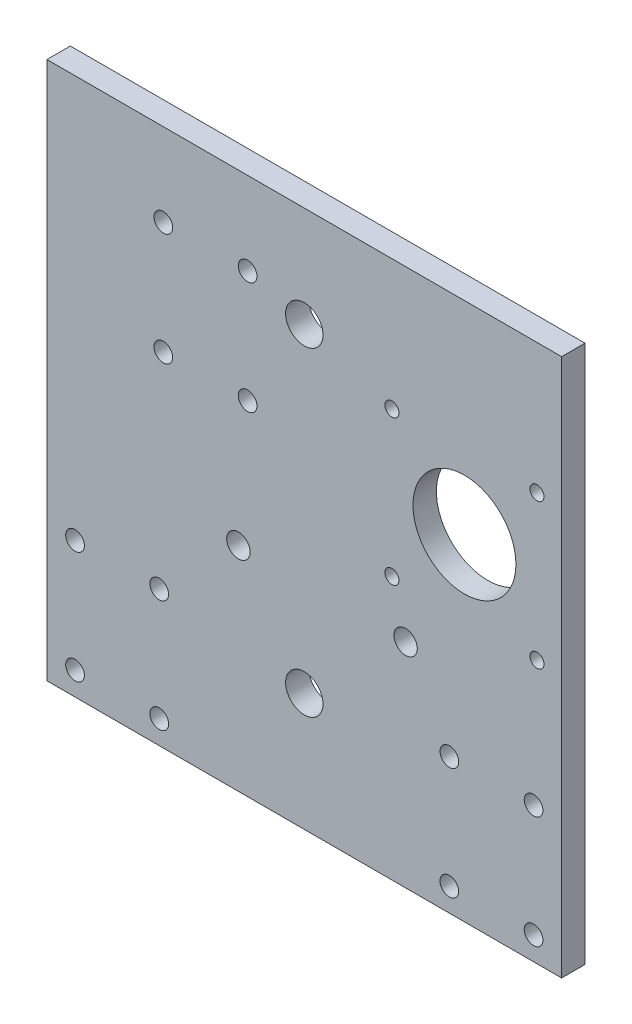
SolidWorks part; units mm, degrees
ref_plane "Front Plane" through (0, 0, 0) normal (0, 0, 1) x (1, 0, 0)
ref_plane "Top Plane" through (0, 0, 0) normal (0, 1, 0) x (1, 0, 0)
ref_plane "Right Plane" through (0, 0, 0) normal (1, 0, 0) x (0, 0, -1)
sketch "Sketch1" plane through (0, 0, 0) normal (0, 0, 1) x (1, 0, 0)
  line L0 (-49, -33.3512) -> (-31, -33.3512) construction
  line L1 (-55, 52.6488) -> (55, 52.6488)
  line L2 (-55, 52.6488) -> (-55, -62.3512)
  line L3 (-55, -62.3512) -> (55, -62.3512)
  line L4 (55, 52.6488) -> (55, -62.3512)
  line L5 (-31, -33.3512) -> (-31, -57.3512) construction
  line L6 (-31, -57.3512) -> (-49, -57.3512) construction
  line L19 (-49, -57.3512) -> (-49, -33.3512) construction
  line L20 (-31, -33.3512) -> (0, -33.3512) construction
  line L21 (31, -33.3512) -> (49, -33.3512) construction
  line L22 (49, -33.3512) -> (49, -57.3512) construction
  line L23 (49, -57.3512) -> (31, -57.3512) construction
  line L24 (31, -57.3512) -> (31, -33.3512) construction
  line L25 (0, 0) -> (0, -62.3512) construction
  line L26 (31, -33.3512) -> (0, -33.3512) construction
  line L27 (0, 0) -> (0, 52.6488) construction
  line L32 (18.7257, 24.8288) -> (49.7257, -6.1712) construction
  line L33 (18.7257, -6.1712) -> (49.7257, 24.8288) construction
  line L34 (-21.1236, 22.9488) -> (-31, -33.3512) construction
  line L39 (-30.1302, 34.9576) -> (-12.1171, 34.9576) construction
  line L44 (-14.0823, -16.8238) -> (21.6513, -16.8238) construction
  line L46 (-12.1171, 34.9576) -> (-12.1171, 10.9401) construction
  line L47 (-12.1171, 10.9401) -> (-30.1302, 10.9401) construction
  line L48 (-30.1302, 10.9401) -> (-30.1302, 34.9576) construction
  line L49 (-30.1302, 34.9576) -> (-12.1171, 10.9401) construction
  line L50 (-12.1171, 34.9576) -> (-30.1302, 10.9401) construction
  line L54 (18.7257, 24.8288) -> (49.7257, 24.8288) construction
  line L55 (49.7257, 24.8288) -> (49.7257, -6.1712) construction
  line L56 (49.7257, -6.1712) -> (18.7257, -6.1712) construction
  line L57 (18.7257, -6.1712) -> (18.7257, 24.8288) construction
  circle A0 centre (-31, -33.3512) radius 2
  circle A1 centre (-49, -33.3512) radius 2
  circle A2 centre (-49, -57.3512) radius 2
  circle A3 centre (-31, -57.3512) radius 2
  circle A4 centre (49, -33.3512) radius 2
  circle A5 centre (31, -33.3512) radius 2
  circle A6 centre (31, -57.3512) radius 2
  circle A7 centre (49, -57.3512) radius 2
  circle A8 centre (34.2257, 9.3288) radius 11
  circle A9 centre (49.7257, 24.8288) radius 1.5
  circle A10 centre (49.7257, -6.1712) radius 1.5
  circle A11 centre (18.7257, -6.1712) radius 1.5
  circle A12 centre (18.7257, 24.8288) radius 1.5
  circle A13 centre (0, 31.1488) radius 4
  circle A14 centre (0, -37.1512) radius 4
  circle A15 centre (-12.1171, 34.9576) radius 2
  circle A16 centre (-30.1302, 34.9576) radius 2
  circle A17 centre (-30.1302, 10.9401) radius 2
  circle A18 centre (-12.1171, 10.9401) radius 2
  circle A19 centre (21.6513, -16.8238) radius 2.5
  circle A20 centre (-14.0823, -16.8238) radius 2.5
  point P0 (0, 0)
  point P12 (-40, -45.3512)
  point P25 (34.2257, 9.3288)
  dimension "D6" = 31
  dimension "D7" = 68.3
  dimension "D1" = 110
  dimension "D2" = 115
  dimension "D3" = 31
  dimension "D4" = 24
  dimension "D5" = 18
  dimension "D9" = 68.3
extrude "Boss-Extrude1" add sketch "Sketch1" along normal blind 5
